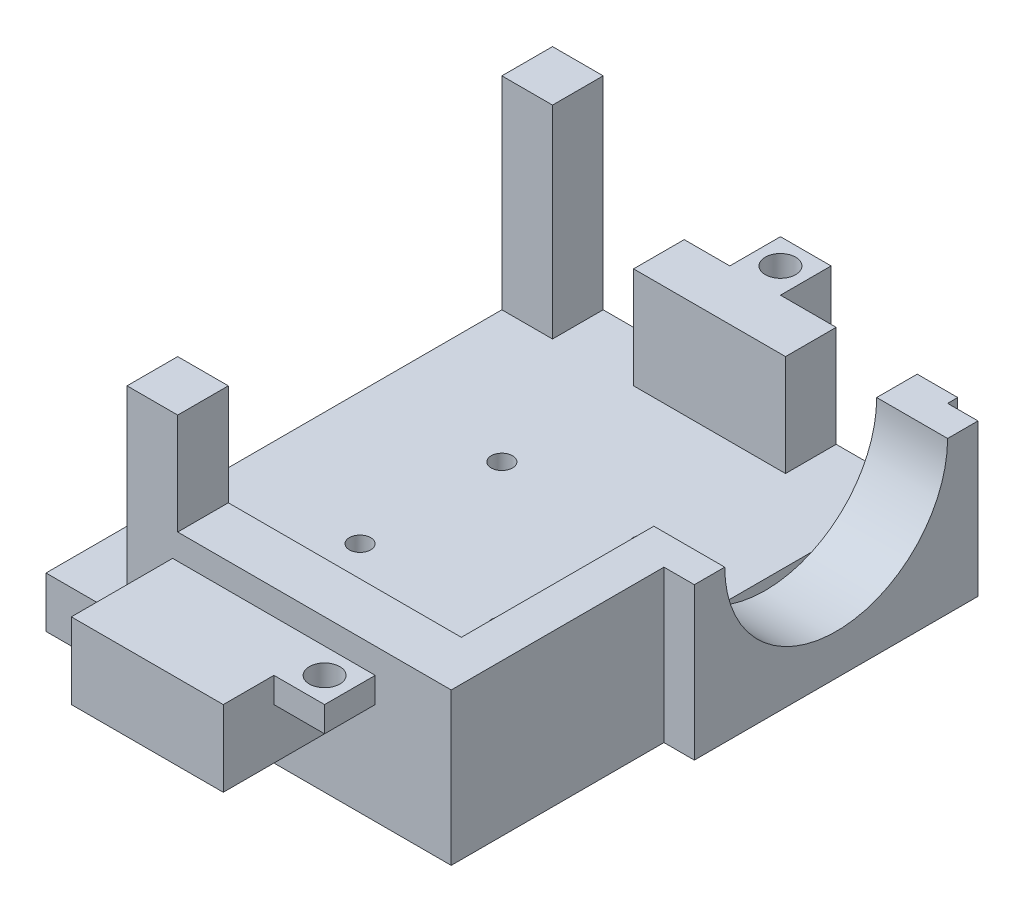
SolidWorks part; units mm, degrees
ref_plane "Front Plane" through (0, 0, 0) normal (0, 0, 1) x (1, 0, 0)
ref_plane "Top Plane" through (0, 0, 0) normal (0, 1, 0) x (1, 0, 0)
ref_plane "Right Plane" through (0, 0, 0) normal (1, 0, 0) x (0, 0, -1)
sketch "Sketch1" plane through (0, 0, 0) normal (0, 1, 0) x (1, 0, 0)
  line L1 (-20, 25) -> (20, 25)
  line L2 (-20, 25) -> (-20, -25)
  line L3 (-20, -25) -> (20, -25)
  line L4 (20, 25) -> (20, -25)
  point P5 (-20, 0)
  point P6 (0, 25)
  dimension "D1" = 40
  dimension "D2" = 50
extrude "Boss-Extrude1" add sketch "Sketch1" along normal blind 5
sketch "Sketch4" plane through (0, 5, 0) normal (0, 1, 0) x (1, 0, 0)
  line L0 (-20, -25) -> (20, -25) construction
  line L1 (20, 25) -> (16, 25)
  line L2 (20, 25) -> (20, -25)
  line L4 (16, 25) -> (16, -20)
  line L5 (20, 25) -> (-20, 25) construction
  line L8 (16, -20) -> (-7, -20)
  line L9 (-7, -25) -> (-7, -20)
  line L10 (-20, 25) -> (-15, 25)
  line L11 (-20, 25) -> (-20, 20)
  line L12 (-20, 20) -> (-15, 20)
  line L13 (-15, 25) -> (-15, 20)
  line L14 (-7, 25) -> (8, 25)
  line L15 (-7, 25) -> (-7, 20)
  line L16 (-7, 20) -> (8, 20)
  line L17 (8, 25) -> (8, 20)
  line L18 (-7, -25) -> (20, -25)
  line L19 (-12, 25) -> (-12, 20) construction
  line L20 (-12, 20) -> (-7, 20) construction
  line L21 (-15, -25) -> (-15, -20) construction
  line L22 (-15, -20) -> (-20, -20) construction
  line L23 (-20, 25) -> (-20, -25) construction
  line L25 (-7, -20) -> (-12, -20)
  line L26 (-7, -20) -> (-7, -25)
  line L27 (-7, -25) -> (-12, -25)
  line L28 (-12, -20) -> (-12, -25)
  line M19 (-20, 25) -> (-20, -25)
  line M20 (-20, -25) -> (20, -25)
  line M21 (20, -25) -> (20, 25)
  line M22 (20, 25) -> (-20, 25)
  dimension "D1" = 4
  dimension "D2" = 5
  dimension "D3" = 5
  dimension "D4" = 15
  dimension "D5" = 5
  dimension "D6" = 8
extrude "Boss-Extrude4" add sketch "Sketch4" along normal blind 20 contours L25 L28 L9 M20 | L13 L12 M22 M19 region at (-9.5, 5, 22.5) region at (-17.5, 5, -22.5)
extrude "Boss-Extrude5" add sketch "Sketch4<4>" along normal blind 10 contours L9 L4 L8 M20 M21 M22 | L17 L15 L16 M22 region at (19.4318, 5, 0) region at (0.5, 5, -22.5)
sketch "Sketch4<4>" plane through (0, 5, 0) normal (0, 1, 0) x (1, 0, 0) same geometry as "Sketch4"
sketch "Sketch7" plane through (20, 0, 0) normal (1, 0, 0) x (0, 0, -1)
  line L0 (-25, 15) -> (25, 15) construction
  line L1 (-1, 15) -> (21, 15)
  line L2 (25, 15) -> (25, 0) construction
  arc A0 (-1, 15) -> (21, 15) centre (10, 15) ccw
  dimension "D1" = 22
  dimension "D2" = 15
extrude "Cut-Extrude2" cut sketch "Sketch7" against normal blind 4
sketch "Sketch8" plane through (20, 0, 0) normal (1, 0, 0) x (0, 0, -1)
  line L0 (-1, 15) -> (-4, 15)
  line L1 (-25, 15) -> (-1, 15) construction
  line L2 (-4, 15) -> (-4, 0)
  line L3 (-25, 0) -> (25, 0) construction
  line L4 (-4, 0) -> (24, 0)
  line L5 (24, 0) -> (24, 15)
  line L6 (21, 15) -> (25, 15) construction
  line L7 (24, 15) -> (21, 15)
  line L8 (25, 15) -> (25, 0) construction
  arc A0 (-1, 15) -> (21, 15) centre (10, 15) ccw
  dimension "D2" = 22
  dimension "D1" = 3
  dimension "D3" = 1
extrude "Boss-Extrude7" add sketch "Sketch8" along normal blind 3
sketch "Sketch11" plane through (0, 0, -25) normal (0, 0, -1) x (-1, 0, 0)
  line L0 (-8, 15) -> (7, 15) construction
  line L1 (2.5, 15) -> (-2.5, 15)
  line L2 (2.5, 15) -> (2.5, 10)
  line L3 (2.5, 10) -> (-2.5, 10)
  line L4 (-2.5, 15) -> (-2.5, 10)
  line L6 (-20, 0) -> (20, 0) construction
  point P8 (0, 0)
  point P9 (0, 10)
  dimension "D1" = 5
  dimension "D2" = 5
extrude "Boss-Extrude8" add sketch "Sketch11" along normal blind 5
sketch "Sketch12" plane through (0, 10, 0) normal (0, -1, 0) x (1, 0, 0)
  line L0 (2.5, -30) -> (-2.5, -30) construction
  line L1 (2.5, -30) -> (2.5, -25) construction
  circle A0 centre (0, -27.5) radius 1.5
  point P6 (0, -30)
  point P10 (2.5, -27.5)
  dimension "D1" = 3
extrude "Cut-Extrude6" cut sketch "Sketch12" against normal blind 5
sketch "Sketch15" plane through (0, 0, 25) normal (0, 0, 1) x (1, 0, 0)
  line L0 (12.5, 15) -> (12.5, 12.5) construction
  line L1 (-7, 15) -> (20, 15) construction
  line L2 (12.5, 12.5) -> (12.5, 10)
  line L3 (12.5, 10) -> (7.5, 10)
  line L4 (7.5, 10) -> (7.5, 5)
  line L5 (7.5, 5) -> (-7.5, 5)
  line L6 (-7.5, 5) -> (-7.5, 12.5)
  line L7 (-7.5, 12.5) -> (12.5, 12.5)
  line L8 (-7.5, 12.5) -> (-7.5, 15) construction
  line L9 (7.5, 10) -> (7.5, 12.5)
  point P6 (0, 5)
  dimension "D1" = 5
  dimension "D2" = 2.5
  dimension "D3" = 2.5
  dimension "D4" = 7.5
  dimension "D5" = 20
extrude "Boss-Extrude11" add sketch "Sketch15" along normal blind 5 contours L9 L3 L2 L7 region at (10, 11.25, 25)
extrude "Boss-Extrude12" add sketch "Sketch15<3>" along normal blind 10 contours L4 L9 L7 L6 L5 region at (0, 8.75, 25)
sketch "Sketch15<3>" plane through (0, 0, 25) normal (0, 0, 1) x (1, 0, 0) same geometry as "Sketch15"
sketch "Sketch16" plane through (0, 10, 0) normal (0, -1, 0) x (1, 0, 0)
  line L0 (12.5, 30) -> (12.5, 25) construction
  line L1 (12.5, 30) -> (7.5, 30) construction
  circle A0 centre (10, 27.5) radius 1.5
  point P4 (12.5, 27.5)
  point P7 (10, 30)
  dimension "D1" = 3
extrude "Cut-Extrude8" cut sketch "Sketch16" against normal blind 2.5
sketch "Sketch18" plane through (0, 0, 0) normal (0, -1, 0) x (1, 0, 0)
  line L0 (20, -25) -> (-20, -25) construction
  line L1 (0, -25) -> (0, 25) construction
  line L2 (-20, 25) -> (20, 25) construction
  line L3 (-20, -25) -> (-20, 25) construction
  line L4 (-20, 0) -> (23, 0) construction
  line L5 (23, 4) -> (23, -24) construction
  line L6 (-7, 7) -> (-7, -7) construction
  line L7 (-7, -7) -> (7, -7) construction
  line L8 (7, -7) -> (7, 7) construction
  line L9 (7, 7) -> (-7, 7) construction
  circle A0 centre (-7, 7) radius 1.05
  circle A1 centre (7, 7) radius 1.05
  circle A2 centre (7, -7) radius 1.05
  circle A3 centre (-7, -7) radius 1.05
  point P17 (0, -7)
  point P18 (-7, 0)
  dimension "D3" = 2.1
  dimension "D1" = 14
  dimension "D2" = 14
extrude "Cut-Extrude9" cut sketch "Sketch18" against normal blind 5
